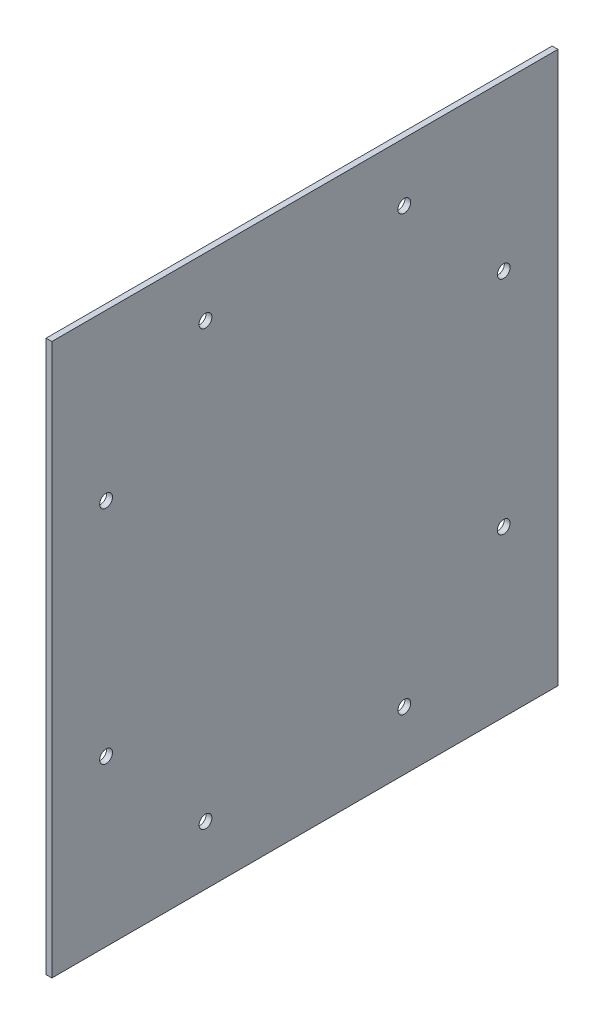
SolidWorks part; units mm, degrees
material "6061-T6 (SS)"
ref_plane "X-Y Datum" through (0, 0, 0) normal (0, 0, 1) x (1, 0, 0)
ref_plane "X-Z Datum" through (0, 0, 0) normal (0, 1, 0) x (1, 0, 0)
ref_plane "Y-Z Datum" through (0, 0, 0) normal (1, 0, 0) x (0, 0, -1)
sketch "Sketch1" plane through (0, 0, 0) normal (1, 0, 0) x (0, 0, -1)
  line L0 (69.85, -152.4) -> (-69.85, -152.4) construction
  line L1 (-177.8, -193.675) -> (177.8, -193.675)
  line L2 (-177.8, -193.675) -> (-177.8, 193.675)
  line L3 (-177.8, 193.675) -> (177.8, 193.675)
  line L4 (177.8, -193.675) -> (177.8, 193.675)
  line L5 (-177.8, -193.675) -> (177.8, 193.675) construction
  line L6 (-177.8, 193.675) -> (177.8, -193.675) construction
  line L7 (-139.7, -77.7875) -> (-139.7, 77.7875) construction
  line L8 (-69.85, -152.4) -> (-139.7, -77.7875) construction
  line L9 (55, 0) -> (-55, 0) construction
  line L10 (0, 55) -> (0, -55) construction
  line L11 (69.85, -152.4) -> (139.7, -77.7875) construction
  line L12 (139.7, -77.7875) -> (139.7, 77.7875) construction
  line L13 (139.7, 77.7875) -> (69.85, 152.4) construction
  line L14 (69.85, 152.4) -> (-69.85, 152.4) construction
  line L15 (-69.85, 152.4) -> (-139.7, 77.7875) construction
  circle A0 centre (69.85, -152.4) radius 4.0005
  circle A1 centre (-69.85, -152.4) radius 4.0005
  circle A2 centre (-139.7, -77.7875) radius 4.0005
  circle A3 centre (-139.7, 77.7875) radius 4.0005
  circle A4 centre (69.85, 152.4) radius 4.0005
  circle A5 centre (-69.85, 152.4) radius 4.0005
  circle A6 centre (139.7, 77.7875) radius 4.0005
  circle A7 centre (139.7, -77.7875) radius 4.0005
  point P0 (0, 0)
  point P10 (0, -152.4)
  point P15 (-139.7, 0)
  dimension "D4" = 8.001
  dimension "D1" = 387.35
  dimension "D2" = 355.6
  dimension "D3" = 41.275
  dimension "D5" = 139.7
  dimension "D6" = 155.575
  dimension "D7" = 38.1
  dimension "D8" = 102.2059
extrude "Boss-Extrude1" add sketch "Sketch1" along normal blind 4.064 contours L1 L4 L3 L2 A6 A4 A3 A2 A1 A0 A5 A7 | A1 | A0 | A7 | A6 | A4 | A5 | A3 | A2 region at (0, 0, 0) region at (0, -152.4, -69.85) region at (0, -152.4, 69.85) region at (0, -77.7875, 139.7) region at (0, 77.7875, 139.7) region at (0, 152.4, -69.85) region at (0, 152.4, 69.85) region at (0, 77.7875, -139.7) region at (0, -77.7875, -139.7)
hole_wizard "M8 Clearance Hole1" positions "Sketch2" profile "Sketch3" hole size "M8" standard "ANSI Metric" end condition through all
sketch "Sketch2" plane through (4.064, 0, 0) normal (1, 0, 0) x (0, 0, -1)
  point P0 (-139.7, 77.7875)
  point P3 (-69.85, 152.4)
  point P6 (69.85, 152.4)
  point P9 (139.7, 77.7875)
  point P12 (139.7, -77.7875)
  point P15 (69.85, -152.4)
  point P18 (-69.85, -152.4)
  point P21 (-139.7, -77.7875)
sketch "Sketch3" plane through (4.064, 77.7875, 139.7) normal (0, 1, 0) x (0, 0, -1)
  line L0 (0, 0) -> (0, 4.064)
  line L1 (0, 4.064) -> (4.5, 4.064)
  line L2 (4.5, 4.064) -> (4.5, 0)
  line L5 (4.5, 0) -> (0, 0)
  line L11 (0, -6.35) -> (0, 107.95) construction
  dimension "Thru Hole Dia." = 9
  dimension "Thru Hole Depth" = 4.064
